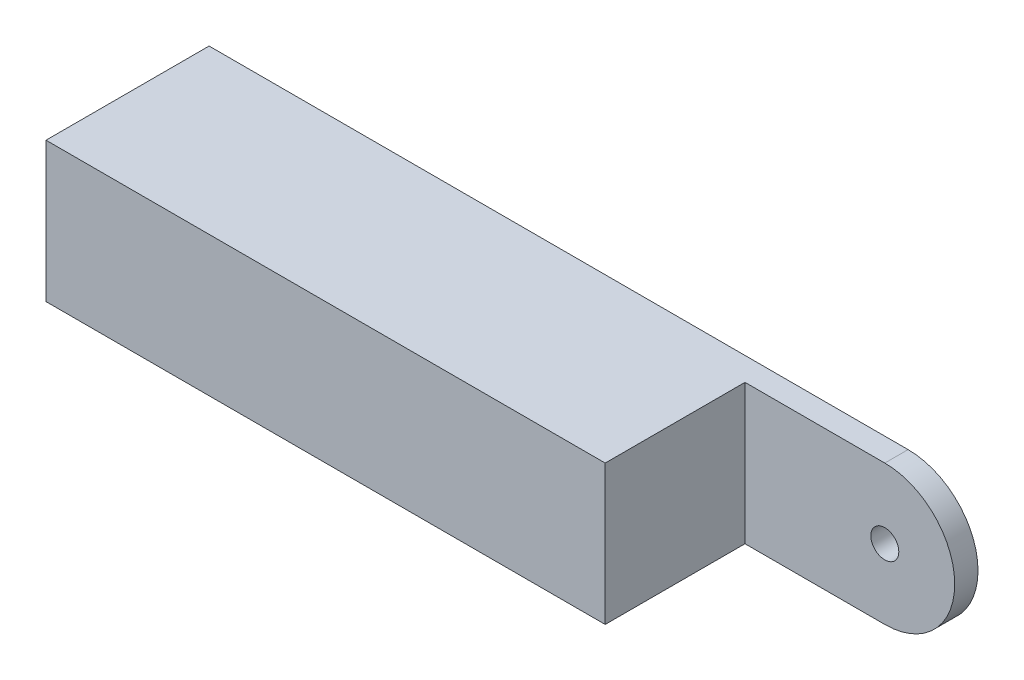
SolidWorks part; units mm, degrees
ref_plane "前视基准面" through (0, 0, 0) normal (0, 0, 1) x (1, 0, 0)
ref_plane "上视基准面" through (0, 0, 0) normal (0, 1, 0) x (1, 0, 0)
ref_plane "右视基准面" through (0, 0, 0) normal (1, 0, 0) x (0, 0, -1)
sketch "草图1" plane through (0, 0, 0) normal (0, 0, 1) x (1, 0, 0)
  line L1 (-60, 15) -> (60, 15)
  line L2 (-60, 15) -> (-60, -15)
  line L3 (-60, -15) -> (60, -15)
  line L4 (60, 15) -> (60, -15)
  line L7 (60, 15) -> (90, 15)
  line L8 (60, 15) -> (60, -15)
  line L9 (60, -15) -> (90, -15)
  arc A0 (90, 15) -> (90, -15) centre (90, 0) cw
  circle A1 centre (90, 0) radius 3
  point P0 (0, 0)
  dimension "D1" = 120
  dimension "D2" = 30
extrude "凸台-拉伸2" add sketch "草图1" along normal blind 35 contours L3 L4 L1 L2
extrude "凸台-拉伸3" add sketch "草图1<8>" along normal blind 5 contours A0 L7 L4 L9 A1 region at (80.8175, 0, 0)
sketch "草图1<8>" plane through (0, 0, 0) normal (0, 0, 1) x (1, 0, 0) same geometry as "草图1"
sketch "草图2" plane through (0, 0, 0) normal (0, 0, -1) x (-1, 0, 0)
  line L0 (60, 15) -> (60, -15) construction
  line L1 (10, 10) -> (50, 10)
  line L2 (10, 10) -> (10, -9.8838)
  line L3 (10, -9.8838) -> (50, -9.8838)
  line L4 (50, 10) -> (50, -9.8838)
  line L5 (60, 15) -> (-90, 15) construction
  dimension "D1" = 10
  dimension "D2" = 5
  dimension "D3" = 40
extrude "切除-拉伸1" cut sketch "草图2" against normal blind 30
